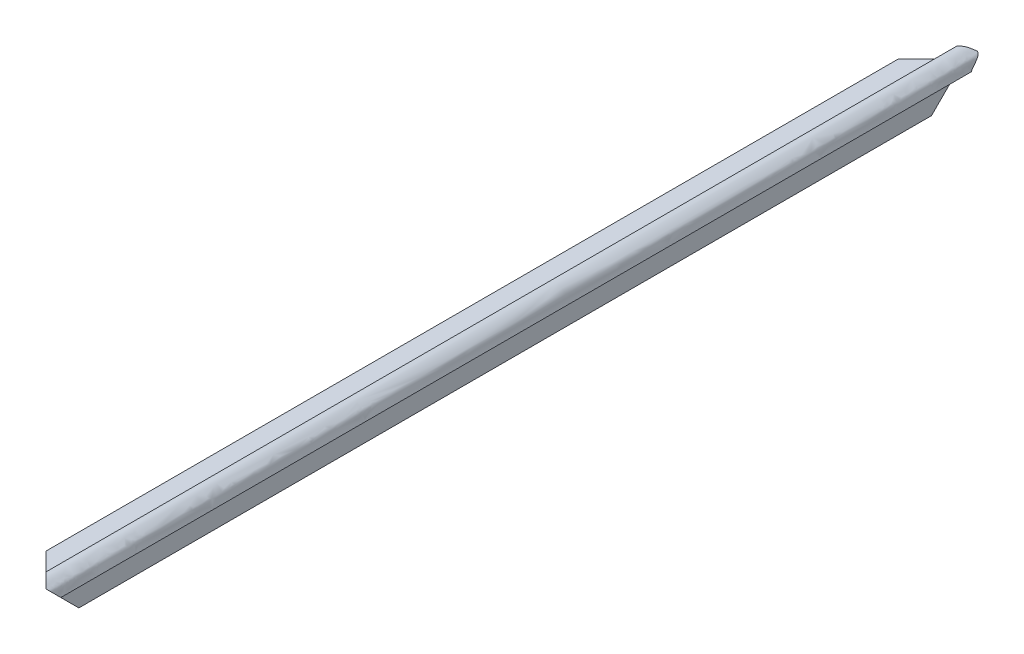
SolidWorks part; units mm, degrees
ref_plane "Front Plane" through (0, 0, 0) normal (0, 0, 1) x (1, 0, 0)
ref_plane "Top Plane" through (0, 0, 0) normal (0, 1, 0) x (1, 0, 0)
ref_plane "Right Plane" through (0, 0, 0) normal (1, 0, 0) x (0, 0, -1)
ref_axis "Axis1" through (0, 0, -88.99) along (0, 0, 1)
sketch "Sketch16" plane through (0, 0, 0) normal (0, 1, 0) x (1, 0, 0)
  line L0 (0, -127) -> (0, 127) construction
  point P2 (0, 0)
  dimension "D1" = 254
sketch "Sketch2" plane through (0, 0, 0) normal (0, 0, 1) x (1, 0, 0)
  line L0 (-10.4775, -1.5) -> (-2.54, -1.5) construction
  line L1 (-10.4775, -1.5) -> (-10.4775, 1.5) construction
  line L2 (-2.54, -1.5) -> (-2.54, 1.5) construction
  line L3 (-10.4775, 1.5) -> (-2.54, 1.5) construction
  line L4 (-2.54, 0) -> (0, 0) construction
  line L5 (0, 0) -> (0, -2.54) construction
  line L6 (-1.5, -2.54) -> (1.5, -2.54) construction
  line L7 (-1.5, -2.54) -> (-1.5, -10.4775) construction
  line L8 (1.5, -2.54) -> (1.5, -10.4775) construction
  line L9 (-1.5, -10.4775) -> (1.5, -10.4775) construction
  point P7 (0, -2.54)
  point P16 (1.5, 1.5)
  dimension "D1" = 3
  dimension "D2" = 7.9375
  dimension "D3" = 2.54
  dimension "D4" = 90
ref_plane "Plane1" through (0, 0, 0) normal (-1, 0, 0) x (0, -1, 0)
sketch "Sketch7" plane through (0, 0, 0) normal (0, 0, 1) x (1, 0, 0)
  line L0 (-10.4775, -1.5) -> (-2.54, -1.5)
  line L1 (-10.4775, -1.5) -> (-10.4775, -4.5)
  line L2 (-2.54, -1.5) -> (-2.54, -4.5)
  line L3 (-10.4775, -4.5) -> (-2.54, -4.5)
  dimension "D1" = 3
extrude "Boss-Extrude2" add sketch "Sketch7" along normal mid plane 260.35 separate body
sketch "Sketch8" plane through (0, 0, 0) normal (0, 0, 1) x (1, 0, 0)
  line L0 (-1.5, -2.54) -> (-1.5, -10.4775)
  line L1 (-1.5, -2.54) -> (-4.5, -2.54)
  line L2 (-1.5, -10.4775) -> (-4.5, -10.4775)
  line L3 (-4.5, -2.54) -> (-4.5, -10.4775)
  line L4 (-2.54, -4.5) -> (-2.54, -1.5) construction
extrude "Boss-Extrude3" add sketch "Sketch8" along normal mid plane 260.35
sketch "Sketch11" plane through (0, 0, 0) normal (0, 0, 1) x (1, 0, 0)
  line L0 (-2.54, 1.5) -> (-2.54, -1.5)
  line L1 (-2.54, -1.5) -> (-10.4775, -1.5)
  line L2 (-10.4775, -1.5) -> (-10.4775, -4.5)
  line L3 (-10.4775, -4.5) -> (-6.7451, -4.5)
  line L4 (-10.4775, -4.5) -> (-4.5, -4.5) construction
  line L5 (-6.7451, -4.5) -> (-4.5, -6.7451)
  line L6 (-4.5, -4.5) -> (-4.5, -10.4775) construction
  line L7 (-4.5, -6.7451) -> (-4.5, -10.4775)
  line L8 (-4.5, -10.4775) -> (-1.5, -10.4775)
  line L9 (-1.5, -10.4775) -> (-1.5, -2.54)
  line L10 (-1.5, -2.54) -> (1.5, -2.54)
  line L11 (-2.54, -0.52) -> (-1.1116, -1.1116) construction
  line L12 (-1.1116, -1.1116) -> (-0.52, -2.54) construction
  line L13 (-2.54, 1.5) -> (-2.54, -2.54) construction
  line L14 (-2.54, -2.54) -> (1.5, -2.54) construction
  line L15 (-2.54, -2.54) -> (0.3167, 0.3167) construction
  line L16 (-2.54, -0.52) -> (-0.52, -2.54) construction
  line L17 (-2.54, -2.54) -> (-0.994, 1.1925) construction
  line L18 (-2.54, -2.54) -> (1.1925, -0.994) construction
  spline S1 degree 3 poles (-2.54, 1.5) (-1.2956, 1.6355) (-0.0425, 0.4732) (1.2977, -0.2922) (1.2637, -2.3404) (1.5, -2.54) knots 0 0 0 0 0.496687 0.741347 0.89974 0.89974 0.89974 0.89974
  dimension "D1" = 3.175
extrude "Boss-Extrude4" add sketch "Sketch11" along normal mid plane 260.35
sketch "Sketch14" plane through (0, 0, 0) normal (0, 1, 0) x (1, 0, 0)
  line L0 (-10.4775, -116.5225) -> (-10.4775, -137.4775)
  line L1 (-10.4775, -130.175) -> (-10.4775, 130.175) construction
  line L2 (-10.4775, -137.4775) -> (10.4775, -137.4775)
  line L4 (10.4775, -137.4775) -> (-10.4775, -116.5225)
  line L5 (0, 88.99) -> (0, -88.99) construction
  line L6 (0, -127) -> (0, 127) construction
  line L8 (-10.4775, 116.5225) -> (10.4775, 137.4775)
  line L9 (10.4775, 137.4775) -> (-10.4775, 137.4775)
  line L10 (-10.4775, 137.4775) -> (-10.4775, 116.5225)
  point P5 (0, -127)
  point P13 (0, 127)
  dimension "D2" = 45
  dimension "D1" = 45
extrude "Cut-Extrude4" cut sketch "Sketch14" against normal through all both and the other way through all
sketch "Sketch17" plane through (0, 0, 0) normal (-1, 0, 0) x (0, -1, 0)
  line L0 (10.4775, 137.4775) -> (10.4775, 116.5225)
  line L2 (10.4775, 116.5225) -> (-10.4775, 137.4775)
  line L3 (-10.4775, 137.4775) -> (10.4775, 137.4775)
  line L4 (10.4775, -116.5225) -> (-10.4775, -137.4775)
  line L5 (-10.4775, -137.4775) -> (10.4775, -137.4775)
  line L6 (10.4775, -137.4775) -> (10.4775, -116.5225)
  point P4 (0, 127)
  point P10 (0, -127)
  dimension "D2" = 45
  dimension "D1" = 45
  dimension "D3" = 10.4775
extrude "Cut-Extrude5" cut sketch "Sketch17" against normal through all both and the other way through all
ref_plane "Midplane" through (0, 0, 0) normal (-0.7071, 0.7071, 0) x (0.7071, 0.7071, 0)
equation "\"plate_thickness\"= 3mm"
equation "\"D1@Sketch2\"=\"plate_thickness\""
equation "\"joiner_lip_width\" = .3125"
equation "\"D2@Sketch2\"=\"joiner_lip_width\""
equation "\"face_gap\"=0.1"
equation "\"D3@Sketch2\"=\"face_gap\""
equation "\"inside_angle\"= 90"
equation "\"joiner_thickness\"= 3mm"
equation "\"edge_length\" = 10"
equation "\"Face1_TopLip\"= 90deg"
equation "\"Face1_BottomLip\"= 90deg"
equation "\"Face2_TopLip\"= 90deg"
equation "\"Face2_BottomLip\"= 90deg"
equation "\"D1@Sketch7\"=\"joiner_thickness\""
equation "\"D1@Boss-Extrude2\"=\"Extrude_to\""
equation "\"D1@Boss-Extrude3\"=\"Extrude_to\""
equation "\"D1@Boss-Extrude4\"=\"Extrude_to\""
equation "\"D4@Sketch2\"=\"inside_angle\""
equation "\"Extrude_to\"= \"edge_length\" + .25"
equation "\"D2@Sketch14\"=\"Face1_BottomLip\"/2"
equation "\"D1@Sketch16\"=\"edge_length\""
equation "\"D1@Sketch14\"=\"Face1_TopLip\"/2"
equation "\"D1@Sketch17\"=\"Face2_TopLip\"/2"
equation "\"D2@Sketch17\"=\"Face2_BottomLip\"/2"
equation "\"D3@Sketch17\"=\"joiner_lip_width\"+\"face_gap\""
equation "\"D2@Sketch5\"=\"Face2_TopLip\"/2"
equation "\"D1@Sketch5\"=\"Face2_BottomLip\"/2"
equation "\"D2@Sketch4\"=\"Face1_TopLip\"/2"
equation "\"D1@Sketch4\"=\"Face1_BottomLip\"/2"
equation "\"D1\" = \"edge_length\""
equation "\"D2@Sketch12\"=\"Face1_TopLip\"/2"
equation "\"D1@Sketch12\"=\"Face1_BottomLip\"/2"
